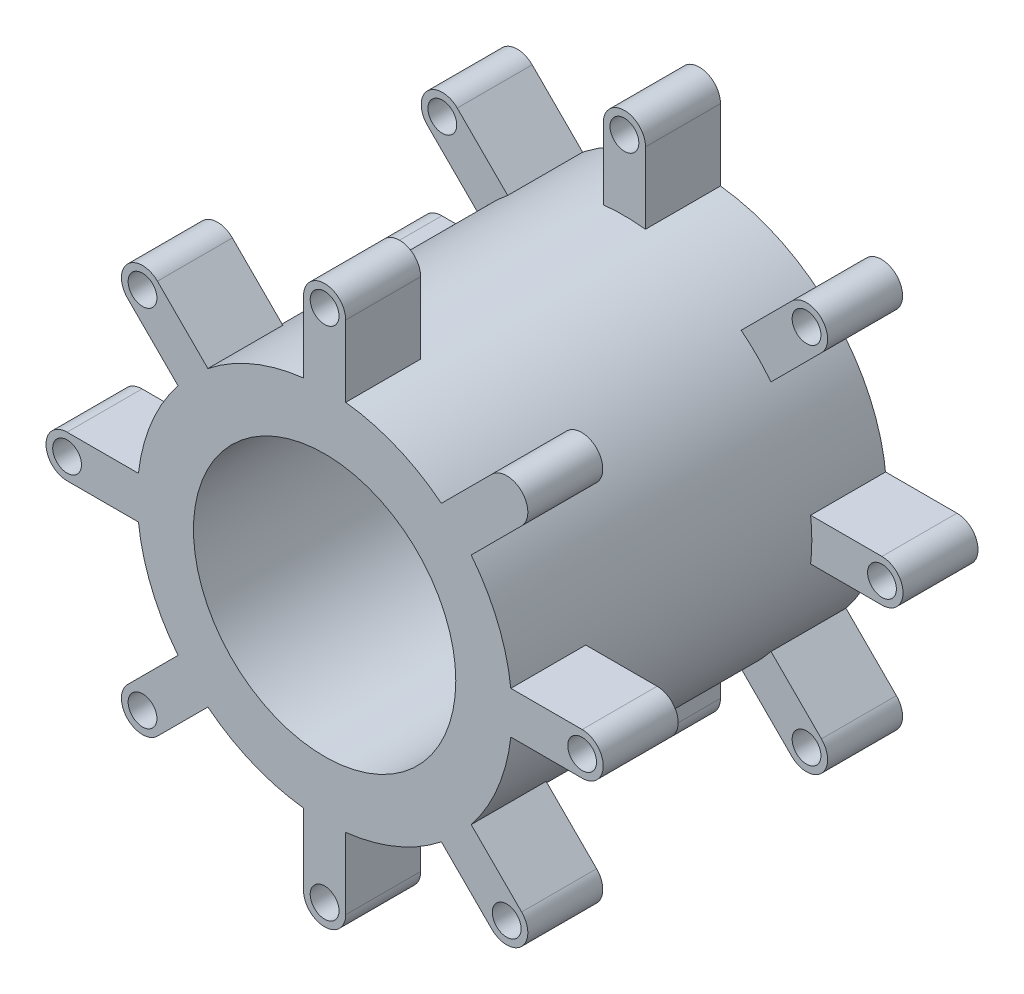
SolidWorks part; units mm, degrees
ref_plane "Front Plane" through (0, 0, 0) normal (0, 0, 1) x (1, 0, 0)
ref_plane "Top Plane" through (0, 0, 0) normal (0, 1, 0) x (1, 0, 0)
ref_plane "Right Plane" through (0, 0, 0) normal (1, 0, 0) x (0, 0, -1)
sketch "Sketch1" plane through (0, 0, 0) normal (0, 0, 1) x (1, 0, 0)
  line L0 (49.6823, 5.6277) -> (68.7168, 5.6277)
  line L1 (49.6823, -5.6277) -> (68.7168, -5.6277)
  line L2 (39.11, -31.1513) -> (52.5695, -44.6108)
  line L3 (31.1513, -39.11) -> (44.6108, -52.5695)
  line L4 (5.6277, -49.6823) -> (5.6277, -68.7168)
  line L5 (-5.6277, -49.6823) -> (-5.6277, -68.7168)
  line L6 (-31.1513, -39.11) -> (-44.6108, -52.5695)
  line L7 (-39.11, -31.1513) -> (-52.5695, -44.6108)
  line L8 (-49.6823, -5.6277) -> (-68.7168, -5.6277)
  line L9 (-49.6823, 5.6277) -> (-68.7168, 5.6277)
  line L10 (-39.11, 31.1513) -> (-52.5695, 44.6108)
  line L11 (-31.1513, 39.11) -> (-44.6108, 52.5695)
  line L12 (-5.6277, 49.6823) -> (-5.6277, 68.7168)
  line L13 (5.6277, 49.6823) -> (5.6277, 68.7168)
  line L14 (31.1513, 39.11) -> (44.6108, 52.5695)
  line L15 (39.11, 31.1513) -> (52.5695, 44.6108)
  circle A0 centre (0, 0) radius 50
  circle A1 centre (0, 0) radius 35
  arc A2 (68.7168, -5.6277) -> (68.7168, 5.6277) centre (68.7168, 0) ccw
  circle A3 centre (68.7168, 0) radius 3.8433
  arc A4 (44.6108, -52.5695) -> (52.5695, -44.6108) centre (48.5901, -48.5901) ccw
  circle A5 centre (48.5901, -48.5901) radius 3.8433
  arc A6 (-5.6277, -68.7168) -> (5.6277, -68.7168) centre (0, -68.7168) ccw
  circle A7 centre (0, -68.7168) radius 3.8433
  arc A8 (-52.5695, -44.6108) -> (-44.6108, -52.5695) centre (-48.5901, -48.5901) ccw
  circle A9 centre (-48.5901, -48.5901) radius 3.8433
  arc A10 (-68.7168, 5.6277) -> (-68.7168, -5.6277) centre (-68.7168, 0) ccw
  circle A11 centre (-68.7168, 0) radius 3.8433
  arc A12 (-44.6108, 52.5695) -> (-52.5695, 44.6108) centre (-48.5901, 48.5901) ccw
  circle A13 centre (-48.5901, 48.5901) radius 3.8433
  arc A14 (5.6277, 68.7168) -> (-5.6277, 68.7168) centre (0, 68.7168) ccw
  circle A15 centre (0, 68.7168) radius 3.8433
  arc A16 (52.5695, 44.6108) -> (44.6108, 52.5695) centre (48.5901, 48.5901) ccw
  circle A17 centre (48.5901, 48.5901) radius 3.8433
  point P11 (0, 0)
  point P63 (0, 0)
  dimension "D1" = 8
extrude "Boss-Extrude1" add sketch "Sketch1" along normal blind 100 contours A0 A1 region at (48.5085, 2.7386, 0)
extrude "Boss-Extrude5" add sketch "Sketch1<5>" along normal blind 20 separate body contours L15 A16 L14 A0 A17 | L1 A2 L0 A0 A3 | L3 A4 L2 A0 A5 | L5 A6 L4 A0 A7 | L13 A14 L12 A0 A15 | L11 A12 L10 A0 A13 | L9 A10 L8 A0 A11 | L7 A8 L6 A0 A9 region at (60.0037, 0, 0) region at (42.429, 42.429, 0) region at (42.429, -42.429, 0) region at (0, 60.0037, 0) region at (0, -60.0037, 0) region at (-42.429, 42.429, 0) region at (-42.429, -42.429, 0) region at (-60.0037, 0, 0)
sketch "Sketch1<5>" plane through (0, 0, 0) normal (0, 0, 1) x (1, 0, 0) same geometry as "Sketch1"
sketch "Sketch2" plane through (0, 0, 100) normal (0, 0, 1) x (1, 0, 0)
  line L0 (-31.1513, 39.11) -> (-44.6108, 52.5695) construction
  line L1 (-52.5695, 44.6108) -> (-39.11, 31.1513) construction
  line L2 (-49.6823, 5.6277) -> (-68.7168, 5.6277) construction
  line L3 (-68.7168, -5.6277) -> (-49.6823, -5.6277) construction
  line L4 (-39.11, -31.1513) -> (-52.5695, -44.6108) construction
  line L5 (-44.6108, -52.5695) -> (-31.1513, -39.11) construction
  line L6 (-5.6277, -49.6823) -> (-5.6277, -68.7168) construction
  line L7 (5.6277, -68.7168) -> (5.6277, -49.6823) construction
  line L8 (31.1513, -39.11) -> (44.6108, -52.5695) construction
  line L9 (52.5695, -44.6108) -> (39.11, -31.1513) construction
  line L10 (49.6823, -5.6277) -> (68.7168, -5.6277) construction
  line L11 (68.7168, 5.6277) -> (49.6823, 5.6277) construction
  line L12 (39.11, 31.1513) -> (52.5695, 44.6108) construction
  line L13 (44.6108, 52.5695) -> (31.1513, 39.11) construction
  line L14 (5.6277, 49.6823) -> (5.6277, 68.7168) construction
  line L15 (-5.6277, 68.7168) -> (-5.6277, 49.6823) construction
  line L16 (-31.1513, 39.11) -> (-44.6108, 52.5695)
  line L17 (-52.5695, 44.6108) -> (-39.11, 31.1513)
  line L18 (-49.6823, 5.6277) -> (-68.7168, 5.6277)
  line L19 (-68.7168, -5.6277) -> (-49.6823, -5.6277)
  line L20 (-39.11, -31.1513) -> (-52.5695, -44.6108)
  line L21 (-44.6108, -52.5695) -> (-31.1513, -39.11)
  line L22 (-5.6277, -49.6823) -> (-5.6277, -68.7168)
  line L23 (5.6277, -68.7168) -> (5.6277, -49.6823)
  line L24 (31.1513, -39.11) -> (44.6108, -52.5695)
  line L25 (52.5695, -44.6108) -> (39.11, -31.1513)
  line L26 (49.6823, -5.6277) -> (68.7168, -5.6277)
  line L27 (68.7168, 5.6277) -> (49.6823, 5.6277)
  line L28 (39.11, 31.1513) -> (52.5695, 44.6108)
  line L29 (44.6108, 52.5695) -> (31.1513, 39.11)
  line L30 (5.6277, 49.6823) -> (5.6277, 68.7168)
  line L31 (-5.6277, 68.7168) -> (-5.6277, 49.6823)
  arc A0 (-44.6108, 52.5695) -> (-52.5695, 44.6108) centre (-48.5901, 48.5901) ccw construction
  arc A1 (-31.1513, 39.11) -> (-39.11, 31.1513) centre (0, 0) ccw construction
  arc A2 (-68.7168, 5.6277) -> (-68.7168, -5.6277) centre (-68.7168, 0) ccw construction
  arc A3 (-49.6823, 5.6277) -> (-49.6823, -5.6277) centre (0, 0) ccw construction
  arc A4 (-52.5695, -44.6108) -> (-44.6108, -52.5695) centre (-48.5901, -48.5901) ccw construction
  arc A5 (-39.11, -31.1513) -> (-31.1513, -39.11) centre (0, 0) ccw construction
  arc A6 (-5.6277, -68.7168) -> (5.6277, -68.7168) centre (0, -68.7168) ccw construction
  arc A7 (-5.6277, -49.6823) -> (5.6277, -49.6823) centre (0, 0) ccw construction
  arc A8 (44.6108, -52.5695) -> (52.5695, -44.6108) centre (48.5901, -48.5901) ccw construction
  arc A9 (31.1513, -39.11) -> (39.11, -31.1513) centre (0, 0) ccw construction
  arc A10 (68.7168, -5.6277) -> (68.7168, 5.6277) centre (68.7168, 0) ccw construction
  arc A11 (49.6823, -5.6277) -> (49.6823, 5.6277) centre (0, 0) ccw construction
  arc A12 (52.5695, 44.6108) -> (44.6108, 52.5695) centre (48.5901, 48.5901) ccw construction
  arc A13 (39.11, 31.1513) -> (31.1513, 39.11) centre (0, 0) ccw construction
  arc A14 (5.6277, 68.7168) -> (-5.6277, 68.7168) centre (0, 68.7168) ccw construction
  arc A15 (5.6277, 49.6823) -> (-5.6277, 49.6823) centre (0, 0) ccw construction
  circle A16 centre (0, 0) radius 50 construction
  arc A17 (-44.6108, 52.5695) -> (-52.5695, 44.6108) centre (-48.5901, 48.5901) ccw
  arc A18 (-31.1513, 39.11) -> (-39.11, 31.1513) centre (0, 0) ccw
  arc A19 (-68.7168, 5.6277) -> (-68.7168, -5.6277) centre (-68.7168, 0) ccw
  arc A20 (-49.6823, 5.6277) -> (-49.6823, -5.6277) centre (0, 0) ccw
  arc A21 (-52.5695, -44.6108) -> (-44.6108, -52.5695) centre (-48.5901, -48.5901) ccw
  arc A22 (-39.11, -31.1513) -> (-31.1513, -39.11) centre (0, 0) ccw
  arc A23 (-5.6277, -68.7168) -> (5.6277, -68.7168) centre (0, -68.7168) ccw
  arc A24 (-5.6277, -49.6823) -> (5.6277, -49.6823) centre (0, 0) ccw
  arc A25 (44.6108, -52.5695) -> (52.5695, -44.6108) centre (48.5901, -48.5901) ccw
  arc A26 (31.1513, -39.11) -> (39.11, -31.1513) centre (0, 0) ccw
  arc A27 (68.7168, -5.6277) -> (68.7168, 5.6277) centre (68.7168, 0) ccw
  arc A28 (49.6823, -5.6277) -> (49.6823, 5.6277) centre (0, 0) ccw
  arc A29 (52.5695, 44.6108) -> (44.6108, 52.5695) centre (48.5901, 48.5901) ccw
  arc A30 (39.11, 31.1513) -> (31.1513, 39.11) centre (0, 0) ccw
  arc A31 (5.6277, 68.7168) -> (-5.6277, 68.7168) centre (0, 68.7168) ccw
  arc A32 (5.6277, 49.6823) -> (-5.6277, 49.6823) centre (0, 0) ccw
  circle A33 centre (0, 0) radius 50
  circle A34 centre (-48.5901, 48.5901) radius 3.8433 construction
  circle A35 centre (-68.7168, 0) radius 3.8433 construction
  circle A36 centre (-48.5901, -48.5901) radius 3.8433 construction
  circle A37 centre (0, -68.7168) radius 3.8433 construction
  circle A38 centre (48.5901, -48.5901) radius 3.8433 construction
  circle A39 centre (68.7168, 0) radius 3.8433 construction
  circle A40 centre (48.5901, 48.5901) radius 3.8433 construction
  circle A41 centre (0, 68.7168) radius 3.8433 construction
  circle A42 centre (-48.5901, 48.5901) radius 3.8433
  circle A43 centre (-68.7168, 0) radius 3.8433
  circle A44 centre (-48.5901, -48.5901) radius 3.8433
  circle A45 centre (0, -68.7168) radius 3.8433
  circle A46 centre (48.5901, -48.5901) radius 3.8433
  circle A47 centre (68.7168, 0) radius 3.8433
  circle A48 centre (48.5901, 48.5901) radius 3.8433
  circle A49 centre (0, 68.7168) radius 3.8433
  circle M35 centre (0, 0) radius 50
extrude "Boss-Extrude6" add sketch "Sketch2" against normal blind 20 contours L26 A27 L27 A47 M35 | L24 A25 L25 A46 M35 | L22 A23 L23 A45 M35 | L20 A21 L21 A44 M35 | L18 A19 L19 A43 M35 | L16 A17 L17 A42 M35 | L30 A31 L31 A49 M35 | L28 A29 L29 A30 region at (-42.429, 42.429, 100) region at (0, 60.0037, 100) region at (-60.0037, 0, 100) region at (-42.429, -42.429, 100) region at (60.0037, 0, 100) region at (0, -60.0037, 100) region at (42.429, -42.429, 100)
